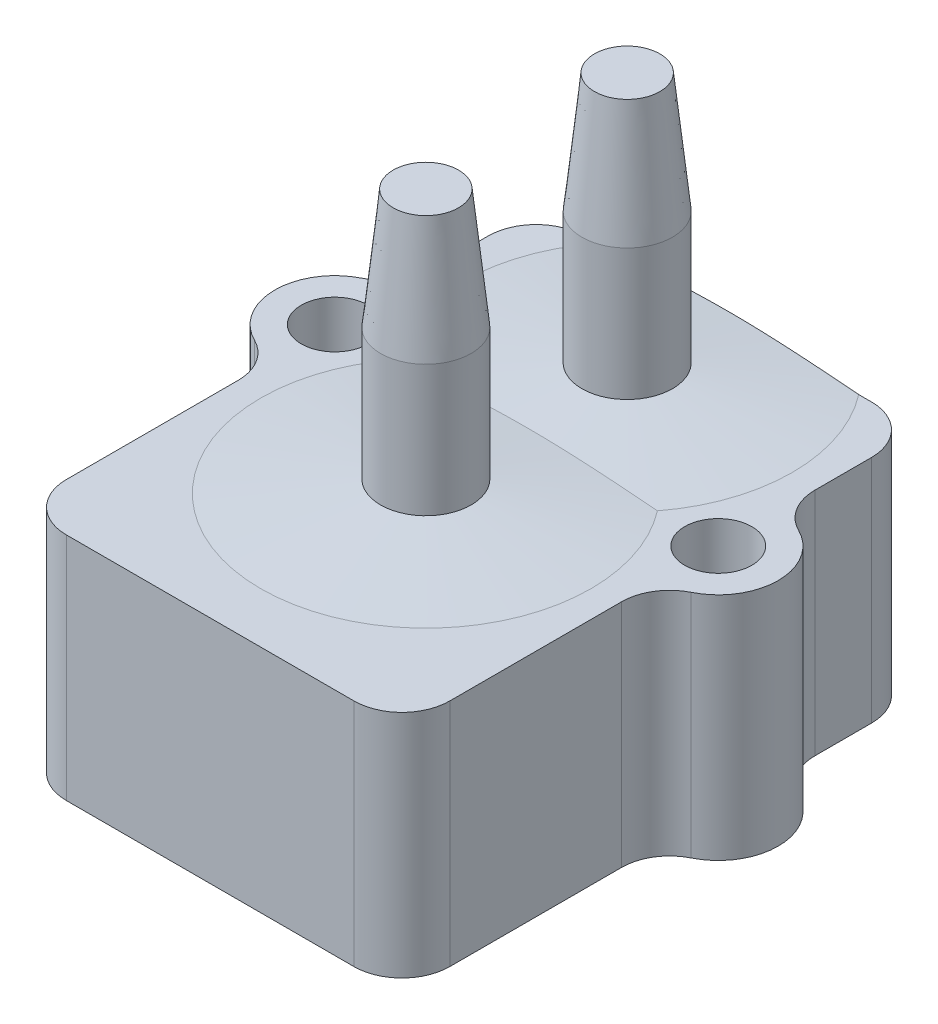
SolidWorks part; units mm, degrees
ref_plane "Front Plane" through (0, 0, 0) normal (0, 0, 1) x (1, 0, 0)
ref_plane "Top Plane" through (0, 0, 0) normal (0, 1, 0) x (1, 0, 0)
ref_plane "Right Plane" through (0, 0, 0) normal (1, 0, 0) x (0, 0, -1)
sketch "Sketch1" plane through (0, 0, 0) normal (0, 1, 0) x (1, 0, 0)
  line L0 (-10.16, 6.223) -> (-10.16, 13.716)
  line L1 (-10.16, -13.716) -> (10.16, -13.716)
  line L2 (-10.16, -13.716) -> (-10.16, -0.127)
  line L3 (-10.16, 13.716) -> (10.16, 13.716)
  line L4 (10.16, -13.716) -> (10.16, -0.127)
  line L5 (-10.16, -13.716) -> (10.16, 13.716) construction
  line L6 (-10.16, 13.716) -> (10.16, -13.716) construction
  line L7 (0, 13.716) -> (0, -13.716) construction
  line L8 (10.16, 6.223) -> (10.16, 13.716)
  arc A0 (-10.16, 6.223) -> (-10.16, -0.127) centre (-10.16, 3.048) ccw
  circle A1 centre (-10.16, 3.048) radius 1.778
  arc A2 (10.16, 6.223) -> (10.16, -0.127) centre (10.16, 3.048) cw
  circle A3 centre (10.16, 3.048) radius 1.778
  point P0 (0, 0)
  dimension "D5" = 3.556
  dimension "D1" = 27.432
  dimension "D2" = 20.32
  dimension "D3" = 6.35
  dimension "D4" = 10.668
extrude "Boss-Extrude1" add sketch "Sketch1" along normal mid plane 12.192
fillet "Fillet1" radius 2.54 8 edges at (-10.16, 0, -6.223) (-10.16, 0, 0.127) (-10.16, 0, -13.716) (10.16, 0, -13.716) (10.16, 0, -6.223) (10.16, 0, 0.127) (10.16, 0, 13.716) (-10.16, 0, 13.716)
sketch "Sketch2" plane through (0, 6.096, 0) normal (0, 1, 0) x (1, 0, 0)
  line L0 (0, 13.716) -> (0, -13.716) construction
  line L1 (7.62, 13.716) -> (-7.62, 13.716) construction
  line L2 (-7.62, -13.716) -> (7.62, -13.716) construction
  circle A0 centre (0, 8.382) radius 2.4003
  circle A1 centre (0, -2.286) radius 2.4003
  dimension "D1" = 4.8006
  dimension "D2" = 10.668
  dimension "D3" = 5.334
extrude "Boss-Extrude2" add sketch "Sketch2" along normal blind 13.97
chamfer "Chamfer1" distance 6.35 angle 6 4 edges at (0, 6.096, 4.6863) (0, 20.066, 4.6863) (0, 6.096, -5.9817) (0, 20.066, -5.9817) first distance on face at (0, 6.096, -5.9817) first distance on face at (0, 20.066, 4.6863) first distance on face at (0, 20.066, -5.9817)
